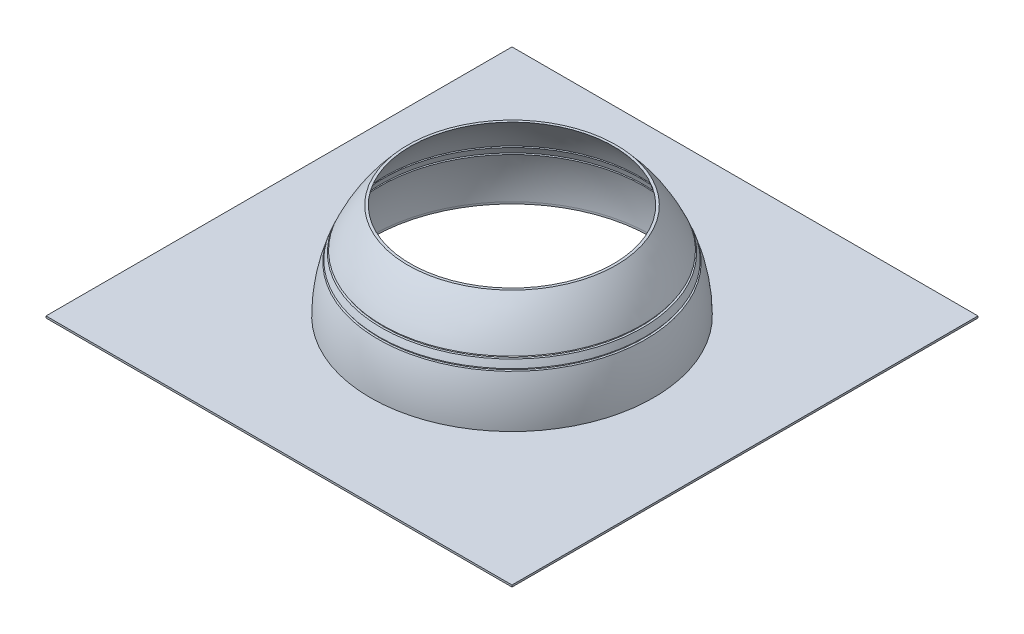
SolidWorks part; units mm, degrees
ref_plane "Front Plane" through (0, 0, 0) normal (0, 0, 1) x (1, 0, 0)
ref_plane "Top Plane" through (0, 0, 0) normal (0, 1, 0) x (1, 0, 0)
ref_plane "Right Plane" through (0, 0, 0) normal (1, 0, 0) x (0, 0, -1)
sketch "Sketch1" plane through (0, 0, 0) normal (0, 1, 0) x (1, 0, 0)
  line L1 (-250, 250) -> (250, 250)
  line L2 (-250, 250) -> (-250, -250)
  line L3 (-250, -250) -> (250, -250)
  line L4 (250, 250) -> (250, -250)
  line L5 (-250, 250) -> (250, -250) construction
  line L6 (-250, -250) -> (250, 250) construction
  point P0 (0, 0)
  dimension "D1" = 500
  dimension "D2" = 500
base flange "Base-Flange1" sketch "Sketch1" thickness 2 reverse thickness direction no parameters "D1"=10
sketch "Sketch7" plane through (0, 0, 0) normal (0, 0, 1) x (1, 0, 0)
  line L0 (0, 194.5015) -> (0, -198.156) construction
  line L1 (-250, 0) -> (250, 0) construction
  line L2 (0, 152) -> (0, 150)
  line L3 (-152, 0) -> (-150, 0)
  arc A0 (0, 150) -> (-150, 0) centre (0, 0) ccw
  arc A1 (0, 152) -> (-152, 0) centre (0, 0) ccw
  dimension "D1" = 300
  dimension "D2" = 2
revolve "Revolve1" add sketch "Sketch7" angle 360 about L0
sketch "Sketch8" plane through (0, 0, 0) normal (0, 0, 1) x (1, 0, 0)
  line L0 (-250, 0) -> (250, 0) construction
  line L1 (-217.2852, 59) -> (184.1961, 59)
  line L2 (-217.2852, 59) -> (-217.2852, 61)
  line L3 (-217.2852, 61) -> (184.1961, 61)
  line L4 (184.1961, 59) -> (184.1961, 61)
  line L5 (-228.3149, 50) -> (265.8159, 50)
  line L6 (-228.3149, 50) -> (-228.3149, 52)
  line L7 (-228.3149, 52) -> (265.8159, 52)
  line L8 (265.8159, 50) -> (265.8159, 52)
  dimension "D1" = 2
  dimension "D2" = 2
  dimension "D3" = 7
  dimension "D4" = 50
extrude "Cut-Extrude1" cut sketch "Sketch8" against normal through all both and the other way through all normal cut yes
sketch "Sketch15" plane through (0, -2, 0) normal (0, -1, 0) x (1, 0, 0)
  circle A0 centre (0, 0) radius 150
  dimension "D1" = 300
extrude "Cut-Extrude2" cut sketch "Sketch15" against normal blind 2 and the other way through all
sketch "Sketch16" plane through (0, 0, 0) normal (0, 0, 1) x (1, 0, 0)
  line L1 (-181.9901, 153) -> (170.9604, 153)
  line L2 (-181.9901, 153) -> (-181.9901, 103)
  line L3 (-181.9901, 103) -> (170.9604, 103)
  line L4 (170.9604, 153) -> (170.9604, 103)
  line L5 (-250, 0) -> (250, 0) construction
  dimension "D1" = 50
  dimension "D2" = 103
extrude "Cut-Extrude3" cut sketch "Sketch16" against normal through all both and the other way through all
sketch "Sketch17" plane through (0, 0, 0) normal (0, 0, 1) x (1, 0, 0)
  line L0 (137.9094, 59) -> (-137.9094, 59) construction
  line L1 (26.3114, 57.5) -> (11.3114, 57.5)
  line L2 (26.3114, 57.5) -> (26.3114, 53.5)
  line L3 (26.3114, 53.5) -> (11.3114, 53.5)
  line L4 (11.3114, 57.5) -> (11.3114, 53.5)
  dimension "D1" = 4
  dimension "D2" = 15
  dimension "D3" = 1.5
extrude "Cut-Extrude5" cut sketch "Sketch17" against normal blind 150
sketch "Bend-Lines1" [suppressed] plane through (0, 0, 0) normal (0, 1, 0) x (1, 0, 0)
sketch "Bounding-Box1" [suppressed] plane through (0, 0, 0) normal (0, 1, 0) x (1, 0, 0)
sheet metal parameters "Sheet-Metal1" thickness 2 parameters "D1"=10
flat pattern "Flat-Pattern1" [suppressed]
sketch "Bend-Lines2" plane through (0, 0, 0) normal (0, 1, 0) x (1, 0, 0)
sketch3d "Bounding-Box2" [suppressed]
  line L0 (-250, -250, 0) -> (250, -250, 0) construction
  line L1 (-250, 250, 0) -> (250, 250, 0) construction
  line L2 (-250, -250, 0) -> (-250, 250, 0) construction
  line L3 (250, -250, 0) -> (250, 250, 0) construction
sheet metal parameters "Sheet-Metal2" thickness 2 parameters "D1"=10
flat pattern "Flat-Pattern1"
sketch "Bend-Lines2" plane through (0, 0, 0) normal (0, 1, 0) x (1, 0, 0)
sketch3d "Bounding-Box2" [suppressed]
  line L0 (250, -250, 0) -> (-250, -250, 0) construction
  line L1 (250, 250, 0) -> (-250, 250, 0) construction
  line L2 (250, -250, 0) -> (250, 250, 0) construction
  line L3 (-250, -250, 0) -> (-250, 250, 0) construction
sheet metal parameters "Sheet-Metal4" thickness 2 parameters "D1"=10
flat pattern "Flat-Pattern4"
sketch "Bend-Lines3" plane through (0, 0, 0) normal (0, 1, 0) x (1, 0, 0)
sketch3d "Bounding-Box3" [suppressed]
  line L0 (250, -250, 0) -> (-250, -250, 0) construction
  line L1 (250, 250, 0) -> (-250, 250, 0) construction
  line L2 (250, -250, 0) -> (250, 250, 0) construction
  line L3 (-250, -250, 0) -> (-250, 250, 0) construction
sheet metal parameters "Sheet-Metal5" thickness 2 parameters "D1"=10
flat pattern "Flat-Pattern5"
sketch "Bend-Lines4" plane through (0, 0, 0) normal (0, 1, 0) x (1, 0, 0)
sketch "Bounding-Box4" [suppressed] plane through (0, 0, 0) normal (0, 1, 0) x (1, 0, 0)
sheet metal parameters "Sheet-Metal6" thickness 2 parameters "D1"=10
flat pattern "Flat-Pattern6"
sketch "Bend-Lines5" plane through (0, 0, 0) normal (0, 1, 0) x (1, 0, 0)
sketch "Bounding-Box5" [suppressed] plane through (0, 0, 0) normal (0, 1, 0) x (1, 0, 0)
sheet metal parameters "Sheet-Metal7" thickness 2 parameters "D1"=10
flat pattern "Flat-Pattern4"
sketch "Bend-Lines3" plane through (0, 0, 0) normal (0, 1, 0) x (1, 0, 0)
sketch3d "Bounding-Box3" [suppressed]
  line L0 (250, -250, 0) -> (-250, -250, 0) construction
  line L1 (250, 250, 0) -> (-250, 250, 0) construction
  line L2 (250, -250, 0) -> (250, 250, 0) construction
  line L3 (-250, -250, 0) -> (-250, 250, 0) construction
sheet metal parameters "Sheet-Metal8" thickness 2 parameters "D1"=10
flat pattern "Flat-Pattern5"
sketch "Bend-Lines4" plane through (0, 0, 0) normal (0, 1, 0) x (1, 0, 0)
sketch "Bounding-Box4" [suppressed] plane through (0, 0, 0) normal (0, 1, 0) x (1, 0, 0)
sheet metal parameters "Sheet-Metal9" thickness 2 parameters "D1"=10
flat pattern "Flat-Pattern6"
sketch "Bend-Lines5" plane through (0, 0, 0) normal (0, 1, 0) x (1, 0, 0)
sketch "Bounding-Box5" [suppressed] plane through (0, 0, 0) normal (0, 1, 0) x (1, 0, 0)
